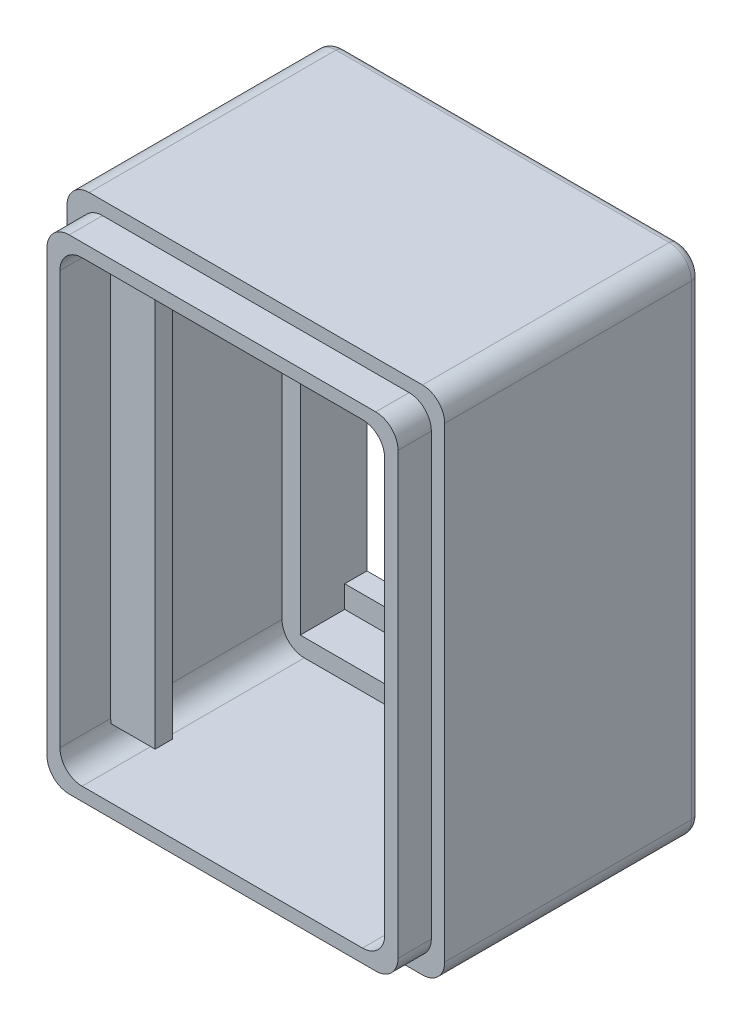
SolidWorks part; units mm, degrees
ref_plane "Front Plane" through (0, 0, 0) normal (0, 0, 1) x (1, 0, 0)
ref_plane "Top Plane" through (0, 0, 0) normal (0, 1, 0) x (1, 0, 0)
ref_plane "Right Plane" through (0, 0, 0) normal (1, 0, 0) x (0, 0, -1)
sketch "Sketch1" plane through (0, 0, 0) normal (0, 0, 1) x (1, 0, 0)
  line L1 (28.0105, 58.42) -> (-15.1695, 58.42)
  line L2 (28.0105, 58.42) -> (28.0105, 0)
  line L3 (28.0105, 0) -> (-15.1695, 0)
  line L4 (-15.1695, 58.42) -> (-15.1695, 0)
  dimension "D1" = 58.42
  dimension "D2" = 43.18
extrude "Boss-Extrude1" add sketch "Sketch1" along normal blind 33.02
sketch "Sketch2" plane through (0, 0, 33.02) normal (0, 0, 1) x (1, 0, 0)
  line L0 (-15.1695, 58.42) -> (-15.1695, 0) construction
  line L1 (-12.1695, 55.372) -> (24.9625, 55.372)
  line L2 (-12.1695, 55.372) -> (-12.1695, 3.048)
  line L3 (-12.1695, 3.048) -> (24.9625, 3.048)
  line L4 (24.9625, 55.372) -> (24.9625, 3.048)
  line L5 (28.0105, 58.42) -> (-15.1695, 58.42) construction
  line L6 (28.0105, 0) -> (28.0105, 58.42) construction
  line L7 (-15.1695, 0) -> (28.0105, 0) construction
  line L9 (-13.6455, 56.896) -> (26.4865, 56.896)
  line L10 (-13.6455, 56.896) -> (-13.6455, 1.524)
  line L11 (-13.6455, 1.524) -> (26.4865, 1.524)
  line L12 (26.4865, 56.896) -> (26.4865, 1.524)
  line L13 (-15.1695, 58.42) -> (28.0105, 58.42)
  line L14 (-15.1695, 58.42) -> (-15.1695, 0)
  line L15 (-15.1695, 0) -> (28.0105, 0)
  line L16 (28.0105, 58.42) -> (28.0105, 0)
  point P22 (-15.1695, 0)
  point P23 (0, 0)
  line M9 (28.0105, 0) -> (28.0105, 58.42)
  line M10 (28.0105, 58.42) -> (-15.1695, 58.42)
  line M11 (-15.1695, 58.42) -> (-15.1695, 0)
  line M12 (-15.1695, 0) -> (28.0105, 0)
  dimension "D1" = 3
  dimension "D2" = 3.048
  dimension "D3" = 3.048
  dimension "D4" = 3.048
  dimension "D5" = 1.524
  dimension "D6" = 1.524
  dimension "D7" = 1.524
  dimension "D8" = 1.524
extrude "Cut-Extrude1" cut sketch "Sketch2" against normal blind 25.4 contours L2 L3 L4 L1
extrude "Cut-Extrude3" cut sketch "Sketch2<6>" against normal blind 3.81 contours L9 L12 L11 L10 M12 M9 M10 M11 region at (6.4205, 57.6935, 33.02)
sketch "Sketch2<6>" plane through (0, 0, 33.02) normal (0, 0, 1) x (1, 0, 0) same geometry as "Sketch2"
sketch "Sketch5" plane through (-12.1695, 0, 0) normal (1, 0, 0) x (0, 0, -1)
  line L0 (-29.21, 58.42) -> (-29.21, 0) construction
  line L1 (-25.21, 53.34) -> (-27.21, 53.34)
  line L2 (-25.21, 53.34) -> (-25.21, 5.08)
  line L3 (-25.21, 5.08) -> (-27.21, 5.08)
  line L4 (-27.21, 53.34) -> (-27.21, 5.08)
  line L5 (-29.21, 0) -> (0, 0) construction
  line L6 (-29.21, 58.42) -> (0, 58.42) construction
  dimension "D1" = 2
  dimension "D2" = 2
  dimension "D3" = 2
  dimension "D4" = 5.08
  dimension "D5" = 5.08
extrude "Boss-Extrude2" add sketch "Sketch5" along normal blind 38.1
sketch "Sketch6" plane through (0, 0, 27.21) normal (0, 0, 1) x (1, 0, 0)
  line L0 (24.9625, 53.34) -> (-12.1695, 53.34) construction
  line L1 (-7.0895, 53.34) -> (19.8825, 53.34)
  line L2 (-7.0895, 53.34) -> (-7.0895, 5.08)
  line L3 (-7.0895, 5.08) -> (19.8825, 5.08)
  line L4 (19.8825, 53.34) -> (19.8825, 5.08)
  line L5 (24.9625, 5.08) -> (-12.1695, 5.08) construction
  line L6 (-12.1695, 55.372) -> (-12.1695, 3.048) construction
  line L7 (24.9625, 55.372) -> (24.9625, 3.048) construction
  dimension "D1" = 5.08
  dimension "D2" = 5.08
extrude "Cut-Extrude4" cut sketch "Sketch6" against normal blind 7.62
sketch "Sketch8" plane through (0, 0, 0) normal (0, 0, -1) x (-1, 0, 0)
  line L0 (-28.0105, 58.42) -> (15.1695, 58.42) construction
  line L1 (-22.9305, 53.34) -> (10.0895, 53.34)
  line L2 (-22.9305, 53.34) -> (-22.9305, 5.08)
  line L3 (-22.9305, 5.08) -> (10.0895, 5.08)
  line L4 (10.0895, 53.34) -> (10.0895, 5.08)
  line L5 (-28.0105, 58.42) -> (-28.0105, 0) construction
  line L6 (15.1695, 58.42) -> (15.1695, 0) construction
  line L7 (15.1695, 0) -> (-28.0105, 0) construction
  dimension "D1" = 5.08
  dimension "D2" = 5.08
  dimension "D3" = 5.08
  dimension "D4" = 5.08
extrude "Cut-Extrude5" cut sketch "Sketch8" against normal blind 7.62
sketch "Sketch9" plane through (0, 5.08, 0) normal (0, 1, 0) x (1, 0, 0)
  line L0 (22.9305, -7.62) -> (22.9305, 0) construction
  line L1 (22.9305, -2.54) -> (-10.0895, -2.54)
  line L2 (22.9305, -2.54) -> (22.9305, 0)
  line L3 (22.9305, 0) -> (-10.0895, 0)
  line L4 (-10.0895, -2.54) -> (-10.0895, 0)
  point P5 (5.3222, -7.852)
  point P6 (2.6397, -1.343)
  point P7 (-1.3512, -4.0245)
  dimension "D1" = 0
  dimension "D2" = 2.54
extrude "Boss-Extrude3" add sketch "Sketch9" along normal blind 2.54
sketch "Sketch11" plane through (0, 53.34, 0) normal (0, -1, 0) x (1, 0, 0)
  line L0 (-10.0895, 7.62) -> (-10.0895, 0) construction
  line L1 (-10.0895, 2.54) -> (22.9305, 2.54)
  line L2 (-10.0895, 2.54) -> (-10.0895, 7.62)
  line L3 (-10.0895, 7.62) -> (22.9305, 7.62)
  line L4 (22.9305, 2.54) -> (22.9305, 7.62)
  line L5 (-10.0895, 7.62) -> (22.9305, 7.62) construction
  line L6 (22.9305, 7.62) -> (22.9305, 0) construction
  dimension "D1" = 0
  dimension "D2" = 0
  dimension "D3" = 0
  dimension "D4" = 5.08
extrude "Boss-Extrude4" add sketch "Sketch11" along normal blind 7.62
sketch "Sketch12" plane through (0, 0, 2.54) normal (0, 0, -1) x (-1, 0, 0)
  line L0 (10.0895, 45.72) -> (-22.9305, 45.72) construction
  line L1 (-12.7705, 47.244) -> (-0.0705, 47.244)
  line L2 (-12.7705, 47.244) -> (-12.7705, 52.324)
  line L3 (-12.7705, 52.324) -> (-0.0705, 52.324)
  line L4 (-0.0705, 47.244) -> (-0.0705, 52.324)
  line L5 (-22.9305, 45.72) -> (-22.9305, 53.34) construction
  line L6 (10.0895, 45.72) -> (10.0895, 53.34) construction
  point P4 (-25.5594, 16.3012)
  dimension "D1" = 1.524
  dimension "D2" = 5.08
  dimension "D3" = 10.16
  dimension "D4" = 10.16
extrude "Cut-Extrude6" cut sketch "Sketch12" against normal blind 3.81
fillet "Fillet1" radius 2.54 4 edges at (-12.1695, 3.048, 20.32) (24.9625, 55.372, 20.32) (24.9625, 3.048, 20.32) (-12.1695, 55.372, 20.32)
fillet "Fillet2" radius 2.54 4 edges at (-15.1695, 58.42, 14.605) (-13.6455, 56.896, 31.115) (26.4865, 56.896, 31.115) (28.0105, 58.42, 14.605)
fillet "Fillet3" radius 2.54 2 edges at (-13.6455, 1.524, 31.115) (-15.1695, 0, 14.605)
fillet "Fillet4" radius 2.54 2 edges at (28.0105, 0, 14.605) (26.4865, 1.524, 31.115)
fillet "Fillet5" radius 1 8 edges at (-14.4256, 0.7439, 0) (-14.4256, 57.6761, 0) (27.2665, 57.6761, 0) (27.2665, 0.7439, 0) (28.0105, 29.21, 0) (6.4205, 58.42, 0) (-15.1695, 29.21, 0) (6.4205, 0, 0)
